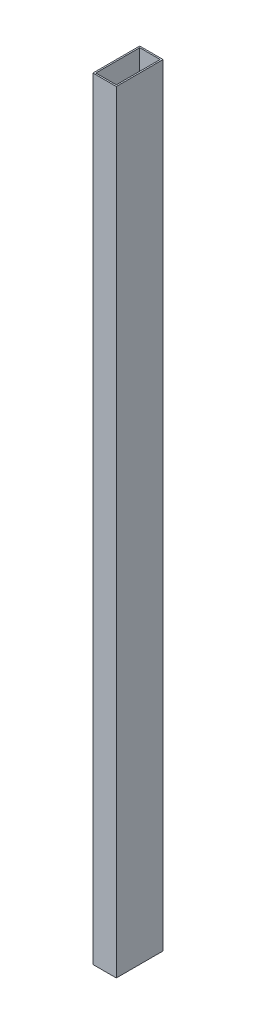
SolidWorks part; units mm, degrees
material "6061-T6 (SS)"
ref_plane "Front" through (0, 0, 0) normal (0, 0, 1) x (1, 0, 0)
ref_plane "Top" through (0, 0, 0) normal (0, 1, 0) x (1, 0, 0)
ref_plane "Right" through (0, 0, 0) normal (1, 0, 0) x (0, 0, -1)
sketch "Sketch1" plane through (0, 0, 0) normal (0, 1, 0) x (1, 0, 0)
  line L1 (12.7, 25.4) -> (-12.7, 25.4)
  line L2 (12.7, 25.4) -> (12.7, -25.4)
  line L3 (12.7, -25.4) -> (-12.7, -25.4)
  line L4 (-12.7, 25.4) -> (-12.7, -25.4)
  line L5 (12.7, 25.4) -> (-12.7, -25.4) construction
  line L6 (12.7, -25.4) -> (-12.7, 25.4) construction
  point P0 (0, 0)
  dimension "D1" = 25.4
  dimension "D2" = 50.8
extrude "Extrude-Thin1" add sketch "Sketch1" along normal blind 838.2 thin thin type one direction reverse wall 1.5875
